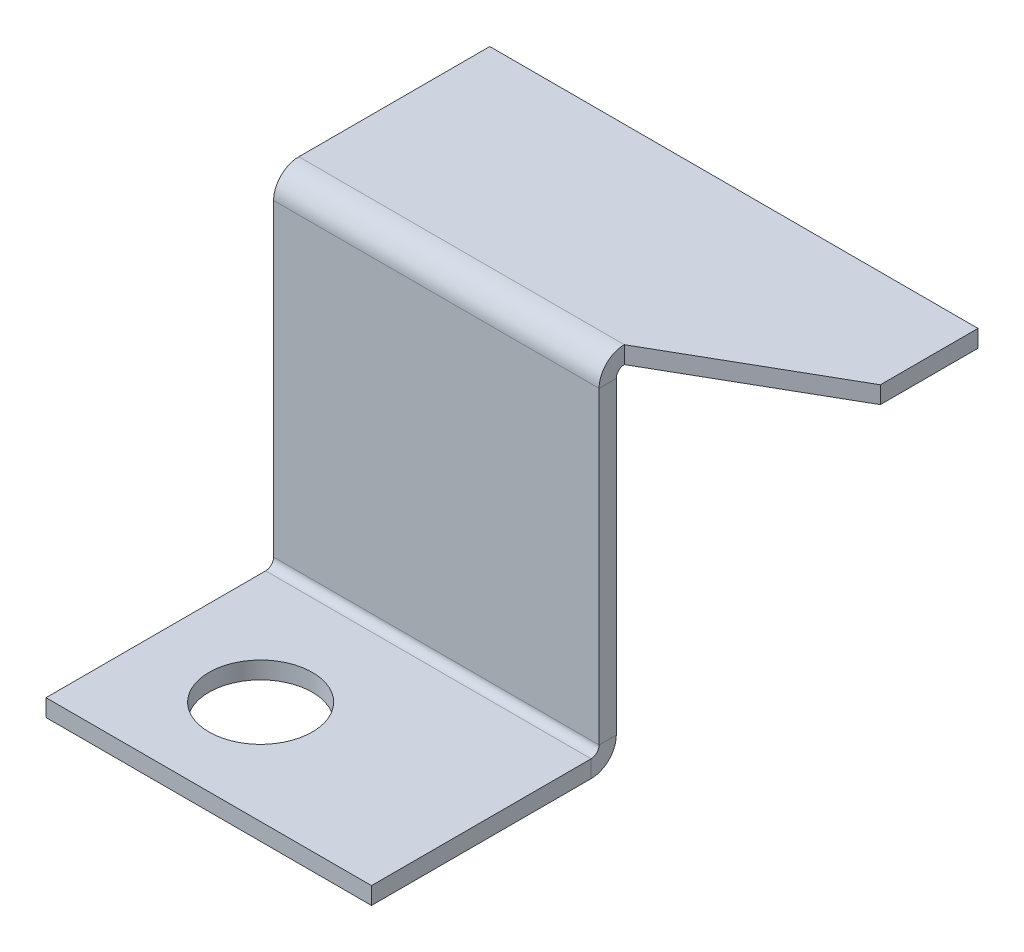
SolidWorks part; units mm, degrees
note: The reader was unsure of these and kept them because the rebuilt part matched: thickness of "Stack Connection", "Edge-Flange1", "Edge-Flange2", "Sheet-Metal5", "Sheet-Metal6", "Sheet-Metal7", "Sheet-Metal8"; flange length of "Edge-Flange1", "Edge-Flange2".
material "Copper"
ref_plane "Front Plane" through (0, 0, 0) normal (0, 0, 1) x (1, 0, 0)
ref_plane "Top Plane" through (0, 0, 0) normal (0, 1, 0) x (1, 0, 0)
ref_plane "Right Plane" through (0, 0, 0) normal (1, 0, 0) x (0, 0, -1)
sketch "Sketch1" plane through (0, 0, 0) normal (0, 1, 0) x (1, 0, 0)
  line L1 (-22.5, 7.5) -> (22.5, 7.5)
  line L2 (-22.5, 7.5) -> (-22.5, -7.5)
  line L3 (-22.5, -7.5) -> (22.5, -7.5)
  line L4 (22.5, 7.5) -> (22.5, -7.5)
  line L5 (-22.5, 7.5) -> (22.5, -7.5) construction
  line L6 (-22.5, -7.5) -> (22.5, 7.5) construction
  point P0 (0, 0)
  dimension "D1" = 15
  dimension "D2" = 45
sketch "Sketch2" plane through (0, 0, 0) normal (0, 1, 0) x (1, 0, 0)
  line L1 (-22.5, 0) -> (22.5, 0)
  line L2 (-22.5, 0) -> (-22.5, -9)
  line L3 (-22.5, -9) -> (-22.5, -17.6)
  line L4 (22.5, 0) -> (22.5, -9)
  line L5 (22.5, -9) -> (7.5, -17.6)
  line L6 (-22.5, -9) -> (22.5, -9) construction
  line L7 (-22.5, -17.6) -> (7.5, -17.6)
  point P0 (0, 0)
  dimension "D3" = 9
  dimension "D1" = 17.6
  dimension "D2" = 45
  dimension "D4" = 30
base flange "Stack Connection" sketch "Sketch2" thickness 1.5875 reverse thickness direction no parameters "D1"=0.7366
edge flange "Edge-Flange1" sketch "Sketch9" flange angle 90 flange length 33.1134 flange position bend outside bend radius 0.7366 thickness 1.5875 relief rectangular parameters "D6"=10
sketch "Sketch9" plane through (0, -1.5875, 17.6) normal (0, 0, 1) x (-1, 0, 0)
  line L2 (-7.5, 0) -> (-7.5, 31.5259)
  line L3 (-7.5, 31.5259) -> (22.5, 31.5259)
  line L4 (22.5, 31.5259) -> (22.5, 0)
  line L7 (22.5, 0) -> (-7.5, 0) construction
  line L8 (22.5, 0) -> (-7.5, 0)
bend "EdgeBend1" bend radius 0.7366 bend angle 90 parameters "D5"=1
edge flange "Edge-Flange2" sketch "Sketch12" flange angle 90 flange length 22.5654 flange position material inside bend radius 0.7366 thickness 1.5875 relief rectangular parameters "D6"=10
sketch "Sketch12" plane through (0, -33.1134, 19.9241) normal (0, -1, 0) x (1, 0, 0)
  line L2 (-22.5, 0) -> (-22.5, 20.9779)
  line L3 (-22.5, 20.9779) -> (7.5, 20.9779)
  line L4 (7.5, 20.9779) -> (7.5, 0)
  line L5 (-22.5, 0) -> (7.5, 0) construction
  line L6 (-22.5, 0) -> (7.5, 0)
bend "EdgeBend2" bend radius 0.7366 bend angle 90 parameters "D5"=2
sketch "Sketch13" plane through (0, -31.5259, 0) normal (0, 1, 0) x (1, 0, 0)
  line L1 (-11.25, -31.3693) -> (-12.25, -31.3693) construction
  line L2 (7.5, -18.3366) -> (-22.5, -18.3366) construction
  circle A0 centre (-12.25, -31.3693) radius 4.7625
  dimension "D1" = 9.525
  dimension "D2" = 1
  dimension "D3" = 13.0327
extrude "Cut-Extrude1" cut sketch "Sketch13" against normal through all normal cut yes
sketch "Bend-Lines1" plane through (0, 0, 0) normal (0, 1, 0) x (1, 0, 0)
sketch "Bounding-Box1" plane through (0, 0, 0) normal (0, 1, 0) x (1, 0, 0)
sheet metal parameters "Sheet-Metal5" thickness 1.5875 parameters "D1"=0.7366
flat pattern "Flat-Pattern5" [suppressed]
sketch "Bend-Lines2" plane through (0, 0, 0) normal (0, 1, 0) x (1, 0, 0)
sketch "Bounding-Box2" [suppressed] plane through (0, 0, 0) normal (0, 1, 0) x (1, 0, 0)
sheet metal parameters "Sheet-Metal6" thickness 1.5875 parameters "D1"=0.7366, "D7"=1
flat pattern "Flat-Pattern5" [suppressed]
sketch "Bend-Lines2" plane through (0, 0, 0) normal (0, 1, 0) x (1, 0, 0)
sketch "Bounding-Box2" [suppressed] plane through (0, 0, 0) normal (0, 1, 0) x (1, 0, 0)
bend of the flat pattern "Flatten-<EdgeBend1>1"
sheet metal parameters "Sheet-Metal7" thickness 1.5875 parameters "D1"=0.7366, "D7"=1
flat pattern "Flat-Pattern5" [suppressed]
sketch "Bend-Lines2" plane through (0, 0, 0) normal (0, 1, 0) x (1, 0, 0)
sketch "Bounding-Box2" [suppressed] plane through (0, 0, 0) normal (0, 1, 0) x (1, 0, 0)
bend of the flat pattern "Flatten-<EdgeBend1>1"
bend of the flat pattern "Flatten-<EdgeBend2>1"
sheet metal parameters "Sheet-Metal8" thickness 1.5875 parameters "D1"=0.7366, "D7"=1
flat pattern "Flat-Pattern5" [suppressed]
sketch "Bend-Lines2" plane through (0, 0, 0) normal (0, 1, 0) x (1, 0, 0)
sketch "Bounding-Box2" [suppressed] plane through (0, 0, 0) normal (0, 1, 0) x (1, 0, 0)
bend of the flat pattern "Flatten-<EdgeBend1>1"
bend of the flat pattern "Flatten-<EdgeBend2>1"
